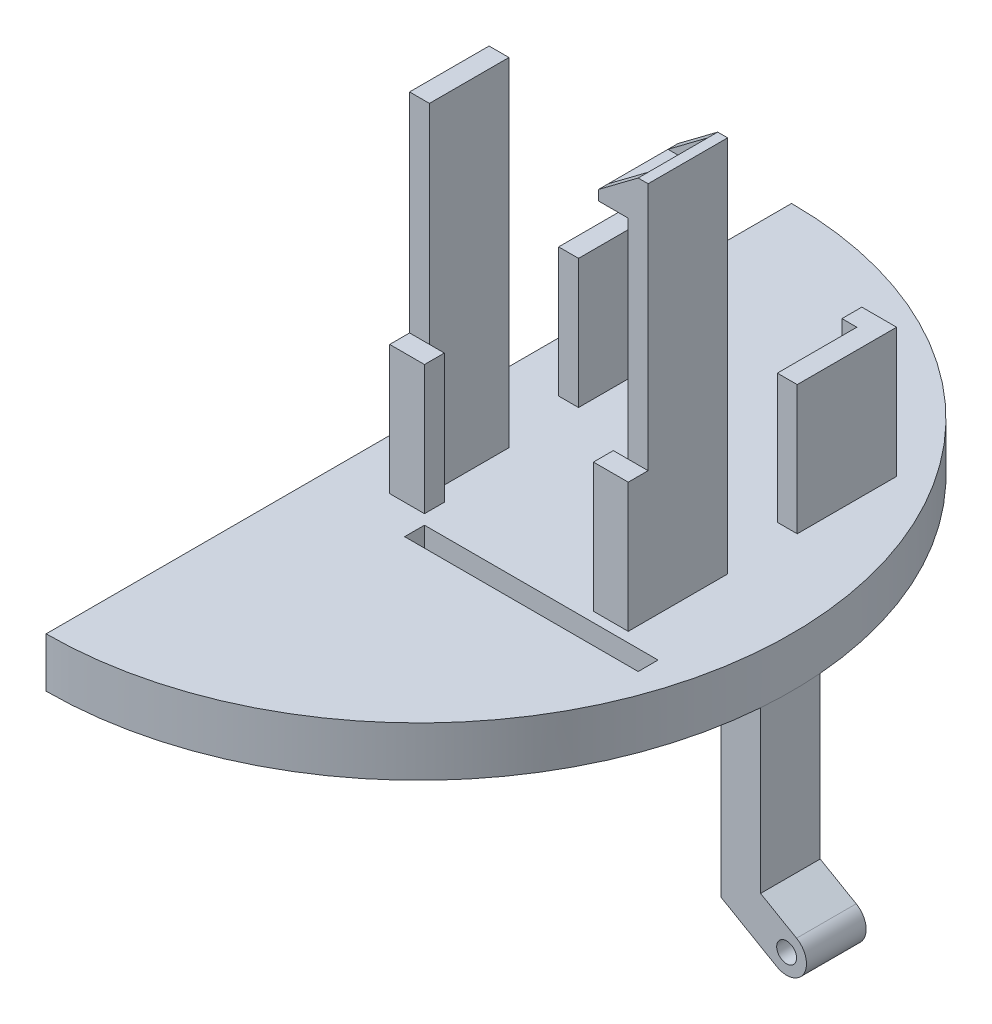
SolidWorks part; units mm, degrees
ref_plane "Ebene vorne" through (0, 0, 0) normal (0, 0, 1) x (1, 0, 0)
ref_plane "Ebene oben" through (0, 0, 0) normal (0, 1, 0) x (1, 0, 0)
ref_plane "Ebene rechts" through (0, 0, 0) normal (1, 0, 0) x (0, 0, -1)
sketch "Skizze1" plane through (0, 0, 0) normal (0, 1, 0) x (1, 0, 0)
  line L0 (0, 0) -> (0, -75)
  arc A0 (0, -75) -> (0, 0) centre (0, -37.5) ccw
  dimension "D1" = 75
extrude "Aufsatz-Linear austragen1" add sketch "Skizze1" along normal blind 5
sketch "Skizze10" plane through (0, 0, 0) normal (0, -1, 0) x (1, 0, 0)
  line L0 (37.3798, 40.5) -> (37.3798, 34.5)
  line L1 (0, 0) -> (0, 75) construction
  arc A0 (0, 0) -> (0, 75) centre (0, 37.5) ccw construction
  dimension "D1" = 6
ref_plane "Ebene1" through (37.3798, 0, 40.5) normal (0, 0, 1) x (1, 0, 0)
sketch "Skizze12" plane through (37.3798, 0, 40.5) normal (0, 0, 1) x (1, 0, 0)
  line L0 (0, 0) -> (0, -16.1778)
  line L2 (1.6202, -21.7321) -> (-4, -18.4872)
  line L3 (-4, 0) -> (0, 0)
  line L4 (-37.3798, 8.8878) -> (-37.3798, -28.7638) construction
  line L5 (2.6202, -15.4311) -> (2.6202, -25.351) construction
  line L6 (4.832, -20) -> (14.1192, -20) construction
  line L7 (-4, -18.4872) -> (-4, 0)
  line L8 (0, -16.1778) -> (3.6202, -18.2679)
  arc A0 (1.6202, -21.7321) -> (3.6202, -18.2679) centre (2.6202, -20) ccw
  point P13 (-1.3964, -16.8336)
  point P14 (4.4992, -6.5118)
  point P17 (-1.4892, -11.2046)
  point P18 (2.8691, -12.2766)
  point P19 (0, 0)
  point P20 (0, 0)
  point P21 (0, 0)
  point P22 (0, 0)
  point P23 (-1.5102, -11.2303)
  point P24 (-4.1078, -22)
  point P25 (-3.1087, -18.3745)
  point P26 (-4.1078, -18.2826)
  point P27 (0, 0)
  point P28 (-4, -18.2947)
  dimension "D1" = 40
  dimension "D2" = 2
  dimension "D4" = 4
  dimension "D3" = 20
  dimension "D5" = 120
extrude "Aufsatz-Linear austragen2" add sketch "Skizze12" against normal up to vertex (6 mm away) contours L0 L8 A0 L2 L7 L3 up to point (37.3798, 0, 34.5)
sketch "Skizze13" plane through (37.3798, 0, 40.5) normal (0, 0, 1) x (1, 0, 0)
  circle A4 centre (2.6202, -20) radius 1
  arc A5 (1.6202, -21.7321) -> (3.6202, -18.2679) centre (2.6202, -20) ccw construction
extrude "Schnitt-Linear austragen1" cut sketch "Skizze13" against normal up to surface (6 mm away) up to face at (37.2085, -12.6108, 34.5)
sketch "Sketch1" plane through (0, 5, 0) normal (0, 1, 0) x (1, 0, 0)
  line L0 (-0.8875, -37.5) -> (-9.8875, -37.5) construction
  line L1 (8.567, -18.5) -> (8.567, -20.5)
  line L2 (7.067, -20.5) -> (8.567, -20.5)
  line L3 (7.067, -20.5) -> (7.067, -28.5)
  line L4 (7.067, -43.5) -> (8.567, -43.5)
  line L5 (27.067, -20.5) -> (27.067, -28.5)
  line L6 (5.067, -18.5) -> (8.567, -18.5)
  line L7 (5.067, -18.5) -> (5.067, -28.5)
  line L8 (5.067, -45.5) -> (8.567, -45.5)
  line L9 (29.067, -18.5) -> (29.067, -28.5)
  line L10 (7.067, -28.5) -> (5.067, -28.5)
  line L11 (7.067, -35.5) -> (5.067, -35.5)
  line L12 (5.067, -35.5) -> (5.067, -45.5)
  line L13 (7.067, -35.5) -> (7.067, -43.5)
  line L14 (25.567, -18.5) -> (25.567, -20.5)
  line L15 (27.067, -28.5) -> (29.067, -28.5)
  line L16 (27.067, -35.5) -> (29.067, -35.5)
  line L17 (25.567, -43.5) -> (25.567, -45.5)
  line L18 (8.567, -43.5) -> (8.567, -45.5)
  line L19 (27.067, -35.5) -> (27.067, -43.5)
  line L20 (29.067, -35.5) -> (29.067, -45.5)
  line L21 (25.567, -45.5) -> (29.067, -45.5)
  line L22 (25.567, -43.5) -> (27.067, -43.5)
  line L23 (25.567, -18.5) -> (29.067, -18.5)
  line L24 (25.567, -20.5) -> (27.067, -20.5)
  dimension "D1" = 23
  dimension "D2" = 20
  dimension "D3" = 2
  dimension "D4" = 1.5
  dimension "D5" = 10
  dimension "D6" = 6
extrude "Boss-Extrude1" add sketch "Sketch1" along normal blind 13
sketch "Sketch2" plane through (0, 18, 0) normal (0, 1, 0) x (1, 0, 0)
  line L0 (29.067, -45.5) -> (29.067, -35.5) construction
  line L1 (27.067, -35.5) -> (29.067, -35.5)
  line L2 (27.067, -35.5) -> (27.067, -43.5)
  line L3 (27.067, -43.5) -> (29.067, -43.5)
  line L4 (29.067, -35.5) -> (29.067, -43.5)
  line L6 (5.067, -35.5) -> (7.067, -35.5)
  line L7 (5.067, -35.5) -> (5.067, -43.5)
  line L8 (5.067, -43.5) -> (7.067, -43.5)
  line L9 (7.067, -35.5) -> (7.067, -43.5)
extrude "Boss-Extrude2" add sketch "Sketch2" along normal blind 21
sketch "Sketch3" plane through (0, 39, 0) normal (0, 1, 0) x (1, 0, 0)
  line L0 (27.067, -35.5) -> (27.067, -43.5) construction
  line L1 (29.067, -35.5) -> (24.067, -35.5)
  line L2 (29.067, -35.5) -> (29.067, -43.5)
  line L3 (29.067, -43.5) -> (24.067, -43.5)
  line L4 (24.067, -35.5) -> (24.067, -43.5)
  line L5 (27.067, -43.5) -> (29.067, -43.5) construction
  dimension "D1" = 3
extrude "Boss-Extrude3" add sketch "Sketch3" along normal blind 1
sketch "Sketch4" plane through (0, 40, 0) normal (0, 1, 0) x (1, 0, 0)
  line L0 (24.067, -35.5) -> (29.067, -35.5)
  line L1 (29.067, -35.5) -> (29.067, -43.5)
  line L2 (29.067, -43.5) -> (24.067, -43.5)
  line L3 (24.067, -43.5) -> (24.067, -42.5)
  line L4 (24.067, -35.5) -> (24.067, -43.5) construction
  line L5 (24.067, -42.5) -> (28.067, -42.5)
  line L6 (28.067, -42.5) -> (28.067, -36.5)
  line L7 (28.067, -36.5) -> (24.067, -36.5)
  line L8 (24.067, -36.5) -> (24.067, -35.5)
  dimension "D1" = 1
  dimension "D2" = 1
extrude "Boss-Extrude4" add sketch "Sketch4" along normal blind 3
sketch "Sketch5" plane through (0, 0, 43.5) normal (0, 0, 1) x (1, 0, 0)
  line L0 (28.067, 43) -> (24.067, 40)
  line L1 (24.067, 43) -> (24.067, 39) construction
  line L2 (24.067, 40) -> (24.067, 43)
  line L3 (24.067, 43) -> (28.067, 43)
  point P5 (0, 0)
extrude "Cut-Extrude1" cut sketch "Sketch5" against normal up to surface (8 mm away) up to face at (26.7337, 29, 35.5)
sketch "Sketch6" plane through (0, 5, 0) normal (0, 1, 0) x (1, 0, 0)
  line L0 (8.567, -45.5) -> (8.567, -43.5) construction
  line L1 (9.567, -46.5) -> (33.067, -46.5)
  line L2 (9.567, -46.5) -> (9.567, -48.5)
  line L3 (9.567, -48.5) -> (33.067, -48.5)
  line L4 (33.067, -46.5) -> (33.067, -48.5)
  line L5 (29.067, -45.5) -> (29.067, -35.5) construction
  line L7 (5.067, -45.5) -> (8.567, -45.5) construction
  dimension "D1" = 1
  dimension "D2" = 4
  dimension "D3" = 2
  dimension "D4" = 1
extrude "Cut-Extrude2" cut sketch "Sketch6" against normal up to next
